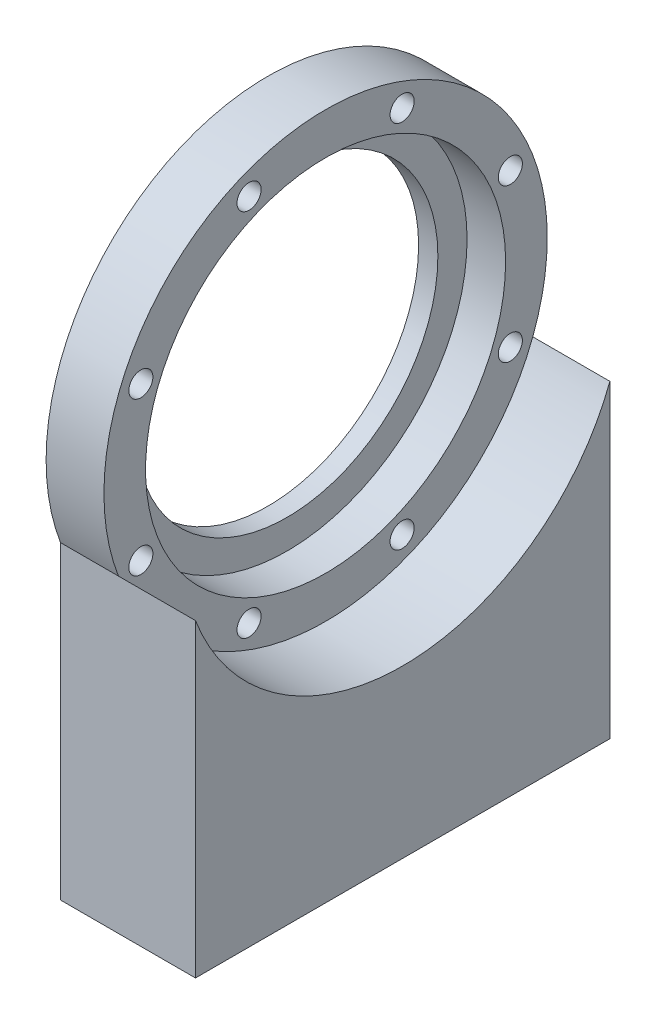
SolidWorks part; units mm, degrees
material "3d打印 35%"
ref_plane "前视基准面" through (0, 0, 0) normal (0, 0, 1) x (1, 0, 0)
ref_plane "上视基准面" through (0, 0, 0) normal (0, 1, 0) x (1, 0, 0)
ref_plane "右视基准面" through (0, 0, 0) normal (1, 0, 0) x (0, 0, -1)
other "Configuration Table"
sketch "草图1" plane through (0, 0, 0) normal (1, 0, 0) x (0, 0, -1)
  line L0 (0, 0) -> (0, 43.0868) construction
  line L1 (0, 0) -> (13.8083, 33.3362) construction
  circle A0 centre (0, 0) radius 23
  circle A1 centre (0, 0) radius 21.6522 construction
  circle A2 centre (0, 0) radius 15.6522
  circle A3 centre (0, 0) radius 18.68
  circle A4 centre (7.9407, 19.1705) radius 1.25
  circle A5 centre (19.1705, 7.9407) radius 1.25
  circle A6 centre (19.1705, -7.9407) radius 1.25
  circle A7 centre (7.9407, -19.1705) radius 1.25
  circle A8 centre (-7.9407, -19.1705) radius 1.25
  circle A9 centre (-19.1705, -7.9407) radius 1.25
  circle A10 centre (-19.1705, 7.9407) radius 1.25
  circle A11 centre (-7.9407, 19.1705) radius 1.25
  point P27 (0, 0)
  dimension "D1" = 8
  dimension "D2" = 46
  dimension "D3" = 2.5
  dimension "D4" = 2.5
  dimension "D5" = 2.5
  dimension "D6" = 20.75
  dimension "D7" = 46
extrude "凸台-拉伸2" add sketch "草图1" along normal blind 2 contours A3 A2 region at (0, 0, 18.1516)
extrude "凸台-拉伸3" add sketch "草图1<4>" along normal blind 6 contours A0 A11 A10 A9 A8 A7 A6 A5 A4 A3 region at (0, 0, 22.3495)
sketch "草图1<4>" plane through (0, 0, 0) normal (1, 0, 0) x (0, 0, -1) same geometry as "草图1"
sketch "草图2" plane through (0, 0, 0) normal (-1, 0, 0) x (0, 0, 1)
  line L0 (-21.5, -40.29) -> (21.5, -40.29)
  line L2 (-21.5, -40.29) -> (-21.5, -8.1701)
  line L4 (21.5, -40.29) -> (21.5, -8.1701)
  line L5 (-16.1624, -40.29) -> (21.5, 0) construction
  line L6 (-21.5, 0) -> (16.1624, -40.29) construction
  circle A0 centre (0, 0) radius 23 construction
  arc A1 (-21.5, -8.1701) -> (21.5, -8.1701) centre (0, 0) ccw
  point P0 (0, -23)
extrude "凸台-拉伸4" add sketch "草图2" against normal blind 14
ref_plane "基准面1" through (7, 0, 0) normal (-1, 0, 0) x (0, 0, 1)
ref_axis "基准轴1" through (7, -40.29, 21.5) along (0, 0, -1)
sketch "草图4" plane through (0, -40.29, 0) normal (0, -1, 0) x (-1, 0, 0)
  line L0 (-14, 21.5) -> (-14, -21.5) construction
  line L2 (-14, -21.5) -> (0, -21.5) construction
  circle A0 centre (-10.5363, -17.5) radius 1.8
  dimension "D1" = 3.4637
  dimension "D2" = 4
extrude "切除-拉伸1" cut sketch "草图4" against normal blind 5
ref_plane "基准面2" through (0, 0, 0) normal (0, 0, 1) x (1, 0, 0)
mirror "镜向1" about plane through (0, 0, 0) normal (0, 0, 1) of "切除-拉伸1"
mirror "镜向2" about plane through (7, 0, 0) normal (-1, 0, 0) of "镜向1"
